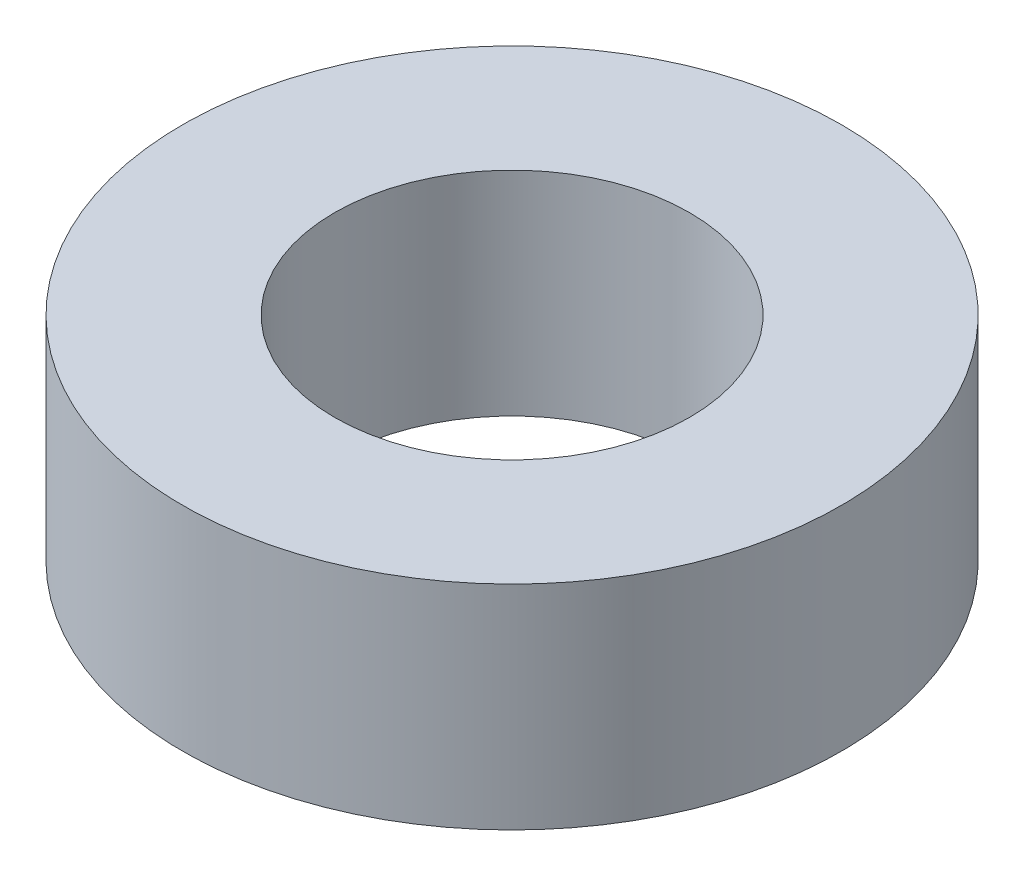
SolidWorks part; units mm, degrees
ref_plane "Front Plane" through (0, 0, 0) normal (0, 0, 1) x (1, 0, 0)
ref_plane "Top Plane" through (0, 0, 0) normal (0, 1, 0) x (1, 0, 0)
ref_plane "Right Plane" through (0, 0, 0) normal (1, 0, 0) x (0, 0, -1)
sketch "Sketch1" plane through (0, 0, 0) normal (0, 1, 0) x (1, 0, 0)
  circle A0 centre (0, 0) radius 32.5
  dimension "FLANGE_OD" = 65
extrude "Boss-Extrude1" add sketch "Sketch1" along normal blind 21
sketch "Sketch2" plane through (0, 0, 0) normal (0, 1, 0) x (1, 0, 0)
  circle A0 centre (0, 0) radius 17.5
  dimension "BORE_D" = 35
extrude "Cut-Extrude1" cut sketch "Sketch2" along normal through all
sketch "Sketch3" plane through (0, 21, 0) normal (0, 1, 0) x (1, 0, 0)
  circle A0 centre (0, 0) radius 12.1727 construction
  circle A1 centre (-12.1727, 0) radius 1.9987
  dimension "BOLT_D" = 3.9975
  dimension "BOLT_PCD" = 24.3454
extrude "Cut-Extrude2" cut sketch "Sketch3" against normal blind 13.6342 rebuild error yes
pattern_circular "CirPattern1" count 4 over 360 rebuild error yes
